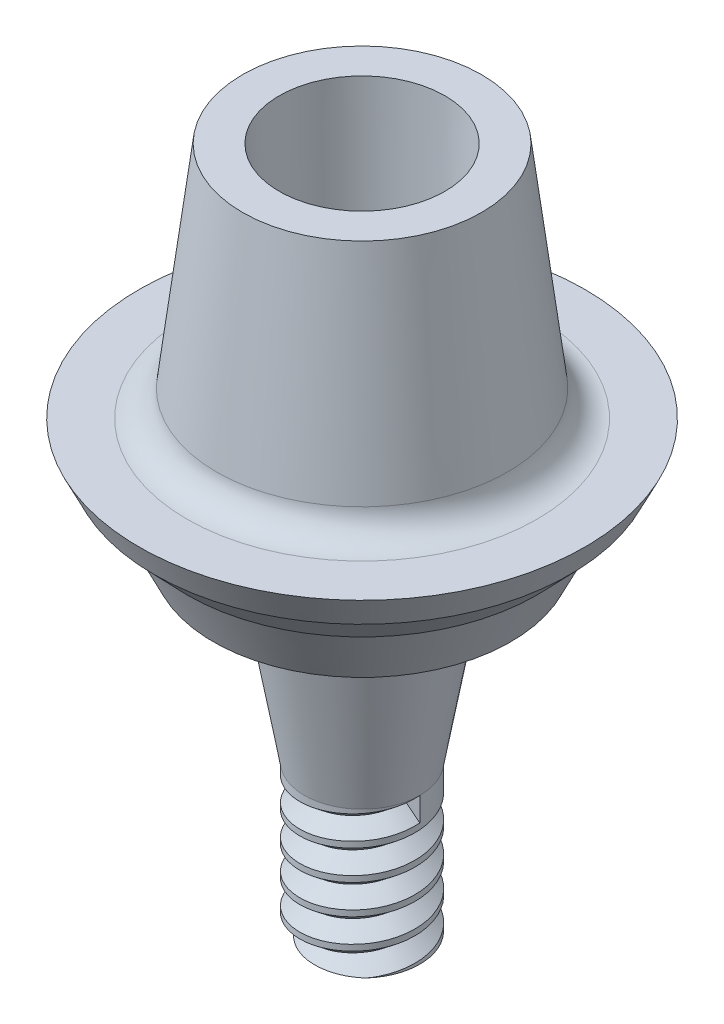
SolidWorks part; units mm, degrees
ref_plane "Plan de face" through (0, 0, 0) normal (0, 0, 1) x (1, 0, 0)
ref_plane "Plan de dessus" through (0, 0, 0) normal (0, 1, 0) x (1, 0, 0)
ref_plane "Plan de droite" through (0, 0, 0) normal (1, 0, 0) x (0, 0, -1)
sketch "Esquisse1" plane through (0, 0, 0) normal (0, 0, 1) x (1, 0, 0)
  line L0 (-3, 0) -> (-1.942, -6)
  line L1 (-3, 0) -> (-5, 0)
  line L2 (0, 0) -> (0, 2)
  line L3 (-5.8688, 1.7935) -> (-6.9847, 2.9509)
  line L4 (-6.9847, 2.9509) -> (-7.5, 4.0147)
  line L5 (-1.942, -6) -> (-1.942, -11)
  line L6 (-1.942, -11) -> (0, -11)
  line L7 (0, -11) -> (0, 0)
  line L8 (-5.8688, 1.7935) -> (-5, 0)
  line L9 (-7.5, 4.0147) -> (-5.8847, 4.0147)
  line L10 (0, 2) -> (0, 4.0147)
  line L11 (-7.5, 4.0147) -> (0, 4.0147) construction
  line L13 (-4.8922, 4.8929) -> (-4.0177, 12.0147)
  line L14 (-4.0177, 12.0147) -> (-2.7869, 12.0147)
  line L15 (-2.7869, 12.0147) -> (-2.5, 4.0147)
  line L16 (-2.5, 4.0147) -> (0, 4.0147)
  arc A0 (-5.8847, 4.0147) -> (-4.8922, 4.8929) centre (-5.8847, 5.0147) ccw
  point P11 (-5, 4.0147)
  point P16 (-25.232, 0.4598)
  point P20 (-4.7933, 0.8321)
  dimension "D2" = 97
  dimension "D10" = 1
  dimension "D3" = 3
  dimension "D4" = 80
  dimension "D5" = 6
  dimension "D6" = 5
  dimension "D7" = 2.5
  dimension "D8" = 8
  dimension "D9" = 2.5
revolve "Révolution1" add sketch "Esquisse1" angle 360 about L7
ref_plane "Plan1" through (0, -6, 0) normal (0, 1, 0) x (1, 0, 0)
sketch "Esquisse2" plane through (0, -6, 0) normal (0, 1, 0) x (1, 0, 0)
  circle A0 centre (0, 0) radius 1.95
curve "Hélice/Spirale1" pitch 1 height 5 radius 1.95 centre (0, -6, 0) axis (0, -1, 0) start towards (1, 0, 0)
sketch "Esquisse3" plane through (0, 0, 0) normal (0, 0, 1) x (1, 0, 0)
  line L0 (1.942, -6) -> (1.942, -6.8)
  line L1 (2.1362, -6) -> (-2.1362, -6) construction
  line L2 (1.942, -11) -> (1.942, -6) construction
  line L5 (1.442, -6.4) -> (1.942, -6)
  line L6 (1.942, -6.8) -> (1.442, -6.4)
  dimension "D1" = 0.8
sketch "Esquisse4" plane through (0, 0, 0) normal (0, 0, 1) x (1, 0, 0)
  line L0 (0, -10.8604) -> (0, -12.4734) construction
  line L2 (0, -12.0701) -> (3.2929, -12.0701)
  line L3 (0, -12.0701) -> (0, -10.9164)
  line L4 (0, -10.9164) -> (3.2929, -10.9164)
  line L5 (3.2929, -12.0701) -> (3.2929, -10.9164)
revolve "Enlèvement de matière-Révolution1" cut sketch "Esquisse4" angle 360 about L0
sweep "Enlèvement de matière-Balayage1" cut profiles "Esquisse3" path "Hélice/Spirale1"
